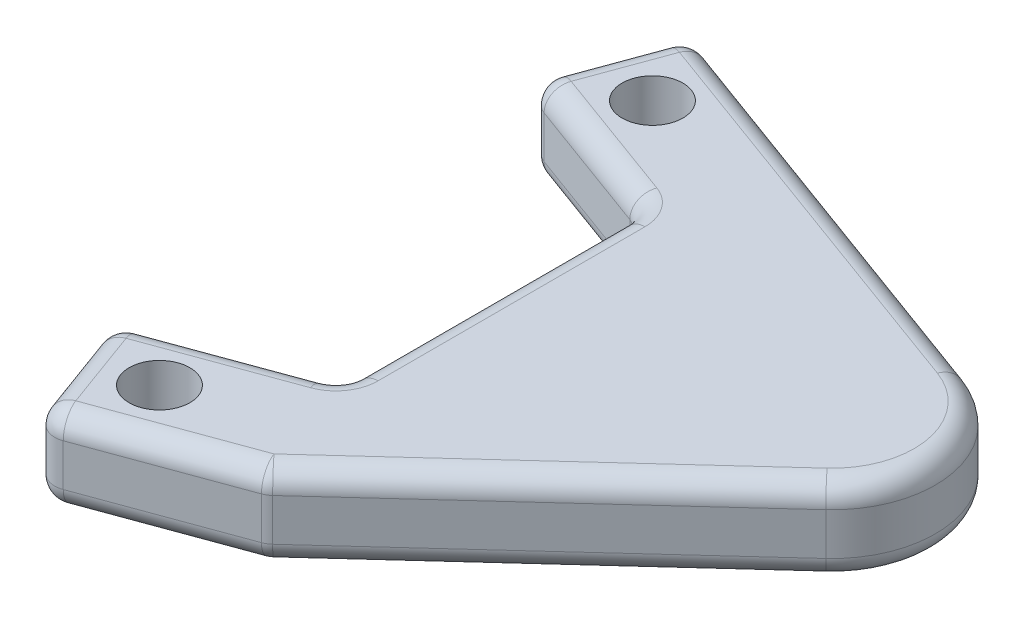
SolidWorks part; units mm, degrees
ref_plane "Front Plane" through (0, 0, 0) normal (0, 0, 1) x (1, 0, 0)
ref_plane "Top Plane" through (0, 0, 0) normal (0, 1, 0) x (1, 0, 0)
ref_plane "Right Plane" through (0, 0, 0) normal (1, 0, 0) x (0, 0, -1)
sketch "Sketch1" plane through (0, 0, 0) normal (0, 1, 0) x (1, 0, 0)
  line L0 (21.2293, -21.8246) -> (53.3227, -33.5685)
  line L7 (30.6561, -57.7105) -> (30.6561, -35.4168)
  line L8 (30.6561, -35.4168) -> (17.9561, -30.7695)
  line L9 (17.9561, -30.7695) -> (21.2293, -21.8246)
  line L11 (21.2293, -71.3027) -> (33.9293, -66.6554)
  line L12 (33.9293, -66.6554) -> (55.8907, -46.5691)
  line L13 (30.6561, -57.7105) -> (17.9561, -62.3578)
  line L14 (-48.9224, -86.8307) -> (30.1351, -57.9011) construction
  line L15 (17.9561, -62.3578) -> (21.2293, -71.3027)
  line L16 (50.6586, -60.5337) -> (-49.8568, -97.3153) construction
  line L25 (30.6561, -57.1557) -> (30.6561, -35.9716) construction
  line L26 (30.1351, -35.2262) -> (-48.9224, -6.2966) construction
  line L29 (-49.8568, 4.188) -> (29.5896, -24.8839) construction
  arc A0 (55.8907, -46.5691) -> (53.3227, -33.5685) centre (50.6586, -40.8487) ccw
  point P1 (33.6277, -66.7658)
  point P2 (59.3758, -35.4168)
  point P4 (58.4109, -35.4168)
  point P10 (61.5807, -46.1368)
  point P19 (60.9932, -36.4121)
  dimension "D1" = 12.7
  dimension "D3" = 12.7
extrude "Boss-Extrude1" add sketch "Sketch1" along normal blind 6.35
sketch "Sketch2" plane through (0, 6.35, 0) normal (0, 1, 0) x (1, 0, 0)
  line L0 (30.6561, -35.4168) -> (30.6561, -57.7105) construction
  line L1 (21.2293, -71.3027) -> (33.9293, -66.6554) construction
  line L2 (24.3061, -65.1055) -> (25.9427, -69.578) construction
  line L4 (24.3061, -65.1055) -> (22.6695, -60.633) construction
  line L5 (30.6561, -57.7105) -> (17.9561, -62.3578) construction
  line L6 (24.3061, -28.0218) -> (22.6695, -32.4943) construction
  line L7 (17.9561, -30.7695) -> (30.6561, -35.4168) construction
  line L8 (24.3061, -28.0218) -> (25.9427, -23.5494) construction
  line L9 (53.3227, -33.5685) -> (21.2293, -21.8246) construction
  line L10 (53.3227, -33.5685) -> (21.2293, -21.8246) construction
  circle A10 centre (24.3061, -65.1055) radius 2.286
  circle A11 centre (24.3061, -28.0218) radius 2.286
  point P0 (25.9427, -23.5494)
  dimension "D1" = 6.35
  dimension "D4" = 4.572
  dimension "D2" = 6.35
extrude "Cut-Extrude1" cut sketch "Sketch2" against normal through all
sketch "Sketch5" plane through (0, 0, 0) normal (0, -1, 0) x (1, 0, 0)
  line L0 (50.6586, 40.8432) -> (57.8976, 40.8432) construction
  line L1 (50.6586, 48.0877) -> (50.6586, 40.8432) construction
  circle A0 centre (50.6586, 40.8432) radius 2.286
  circle A1 centre (50.6586, 40.8487) radius 7.239 construction
  dimension "D1" = 4.572
extrude "Cut-Extrude2" cut sketch "Sketch5" against normal offset from surface (4.7625 mm away) 1.5875 contours A0 up to face at (24.3061, 6.35, 67.3915)
fillet "Fillet1" radius 1.5875 25 edges at (24.3061, 6.35, 33.0932) (24.3061, 0, 33.0932) (24.3061, 6.35, 60.0341) (24.3061, 0, 60.0341) (37.276, 6.35, 27.6965) (58.2639, 6.35, 39.3464) (37.276, 0, 27.6965) (58.2639, 0, 39.3464) (30.6561, 3.175, 35.4168) (30.6561, 6.35, 46.5637) (30.6561, 3.175, 57.7105) (30.6561, 0, 46.5637) (21.2293, 3.175, 21.8246) (19.5927, 6.35, 26.297) (17.9561, 3.175, 30.7695) (19.5927, 0, 26.297) (44.91, 6.35, 56.6123) (44.91, 0, 56.6123) (27.5793, 6.35, 68.9791) (33.9293, 3.175, 66.6554) (27.5793, 0, 68.9791) (17.9561, 3.175, 62.3578) (19.5927, 6.35, 66.8303) (21.2293, 3.175, 71.3027) (19.5927, 0, 66.8303)
